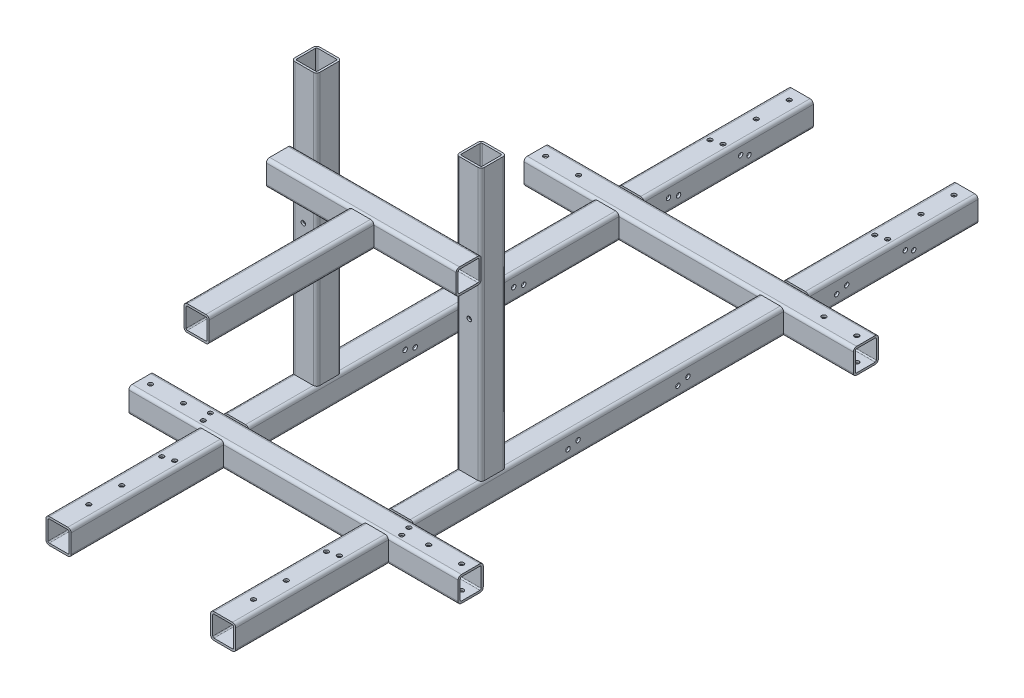
SolidWorks part; units mm, degrees
material "Alumina"
ref_plane "Front Plane" through (0, 0, 0) normal (0, 0, 1) x (1, 0, 0)
ref_plane "Top Plane" through (0, 0, 0) normal (0, 1, 0) x (1, 0, 0)
ref_plane "Right Plane" through (0, 0, 0) normal (1, 0, 0) x (0, 0, -1)
ref_plane "Bottom Face" through (0, 0, 0) normal (0, 1, 0) x (1, 0, 0)
ref_plane "Top Face" through (0, 38.1, 0) normal (0, 1, 0) x (1, 0, 0)
ref_plane "Mid Plane" through (0, 19.05, 0) normal (0, 1, 0) x (1, 0, 0)
ref_plane "Front Face" through (0, 0, 500) normal (0, 0, 1) x (1, 0, 0)
ref_plane "Back Face" through (0, 0, -500) normal (0, 0, 1) x (1, 0, 0)
ref_plane "Left Face" through (250, 0, 0) normal (1, 0, 0) x (0, 0, -1)
ref_plane "Right Face" through (-250, 0, 0) normal (1, 0, 0) x (0, 0, -1)
ref_plane "Divider Plane" through (0, 0, 140) normal (0, 0, 1) x (1, 0, 0)
ref_plane "Max Height Plane" through (0, 450, 0) normal (0, 1, 0) x (1, 0, 0)
ref_plane "Electronics Box Plane" through (0, 338.1, 0) normal (0, 1, 0) x (1, 0, 0)
sketch "Sketch2" plane through (250, 0, 0) normal (1, 0, 0) x (0, 0, -1)
  line L0 (330, 38.1) -> (-330, 38.1) construction
  line L5 (330, 0) -> (-330, 0) construction
  line L6 (0, 220) -> (0, -220) construction
  line L7 (-314.05, 38.1) -> (-285.95, 38.1)
  line L8 (-280.95, 33.1) -> (-280.95, 5)
  line L9 (-315.875, 33.1) -> (-315.875, 5)
  line L10 (-314.05, 3.175) -> (-285.95, 3.175)
  line L11 (-285.95, 0) -> (-314.05, 0)
  line L12 (-319.05, 5) -> (-319.05, 33.1)
  line L13 (-300, 38.1) -> (-300, 0) construction
  line L14 (-319.05, 19.05) -> (-280.95, 19.05) construction
  line L15 (-284.125, 5) -> (-284.125, 33.1)
  line L16 (-285.95, 34.925) -> (-314.05, 34.925)
  line L17 (-300, 34.925) -> (-300, 3.175) construction
  line L18 (-315.875, 19.05) -> (-284.125, 19.05) construction
  arc A0 (-285.95, 38.1) -> (-280.95, 33.1) centre (-285.95, 33.1) cw
  arc A1 (-280.95, 5) -> (-285.95, 0) centre (-285.95, 5) cw
  arc A2 (-314.05, 0) -> (-319.05, 5) centre (-314.05, 5) cw
  arc A3 (-319.05, 33.1) -> (-314.05, 38.1) centre (-314.05, 33.1) cw
  arc A4 (-315.875, 5) -> (-314.05, 3.175) centre (-314.05, 5) ccw
  arc A5 (-285.95, 3.175) -> (-284.125, 5) centre (-285.95, 5) ccw
  arc A6 (-284.125, 33.1) -> (-285.95, 34.925) centre (-285.95, 33.1) ccw
  arc A7 (-314.05, 34.925) -> (-315.875, 33.1) centre (-314.05, 33.1) ccw
  point P20 (-300, 19.05)
  point P39 (-300, 19.05)
  dimension "D1" = 5
  dimension "D2" = 300
  dimension "D3" = 3.175
extrude "Front Cross-Car Member" add sketch "Sketch2" against normal up to surface (500 mm away) up to plane "Right Face"
sketch "Sketch5" plane through (250, 0, 0) normal (1, 0, 0) x (0, 0, -1)
  line L0 (285.95, 38.1) -> (314.05, 38.1)
  line L1 (319.05, 33.1) -> (319.05, 5)
  line L2 (314.05, 0) -> (285.95, 0)
  line L3 (280.95, 5) -> (280.95, 33.1)
  line L4 (300, 38.1) -> (300, 0) construction
  line L5 (280.95, 19.05) -> (319.05, 19.05) construction
  line L6 (285.95, 34.925) -> (314.05, 34.925)
  line L7 (315.875, 33.1) -> (315.875, 5)
  line L8 (314.05, 3.175) -> (285.95, 3.175)
  line L9 (284.125, 5) -> (284.125, 33.1)
  line L10 (300, 34.925) -> (300, 3.175) construction
  line L11 (284.125, 19.05) -> (315.875, 19.05) construction
  line L12 (330, 0) -> (-330, 0) construction
  line L14 (330, 38.1) -> (-330, 38.1) construction
  line L15 (0, 220) -> (0, -220) construction
  arc A0 (314.05, 38.1) -> (319.05, 33.1) centre (314.05, 33.1) cw
  arc A1 (319.05, 5) -> (314.05, 0) centre (314.05, 5) cw
  arc A2 (285.95, 0) -> (280.95, 5) centre (285.95, 5) cw
  arc A3 (280.95, 33.1) -> (285.95, 38.1) centre (285.95, 33.1) cw
  arc A4 (314.05, 34.925) -> (315.875, 33.1) centre (314.05, 33.1) cw
  arc A5 (315.875, 5) -> (314.05, 3.175) centre (314.05, 5) cw
  arc A6 (285.95, 3.175) -> (284.125, 5) centre (285.95, 5) cw
  arc A7 (284.125, 33.1) -> (285.95, 34.925) centre (285.95, 33.1) cw
  point P32 (300, 19.05)
  point P33 (300, 19.05)
  dimension "D2" = 5
  dimension "D1" = 3.175
  dimension "D3" = 300
extrude "Back Cross-Car Member" add sketch "Sketch5" against normal up to surface (500 mm away) separate body up to plane "Right Face"
sketch "Sketch6" plane through (0, 0, -500) normal (0, 0, 1) x (1, 0, 0)
  line L0 (110.95, 38.1) -> (139.05, 38.1)
  line L1 (144.05, 33.1) -> (144.05, 5)
  line L2 (109.125, 33.1) -> (109.125, 5)
  line L3 (110.95, 3.175) -> (139.05, 3.175)
  line L4 (139.05, 0) -> (110.95, 0)
  line L5 (105.95, 5) -> (105.95, 33.1)
  line L6 (125, 38.1) -> (125, 0) construction
  line L7 (105.95, 19.05) -> (144.05, 19.05) construction
  line L8 (140.875, 5) -> (140.875, 33.1)
  line L9 (139.05, 34.925) -> (110.95, 34.925)
  line L10 (125, 34.925) -> (125, 3.175) construction
  line L11 (109.125, 19.05) -> (140.875, 19.05) construction
  line L12 (330, 38.1) -> (-330, 38.1) construction
  line L13 (330, 0) -> (-330, 0) construction
  line L14 (0, -220) -> (0, 220) construction
  arc A0 (139.05, 38.1) -> (144.05, 33.1) centre (139.05, 33.1) cw
  arc A1 (144.05, 5) -> (139.05, 0) centre (139.05, 5) cw
  arc A2 (110.95, 0) -> (105.95, 5) centre (110.95, 5) cw
  arc A3 (105.95, 33.1) -> (110.95, 38.1) centre (110.95, 33.1) cw
  arc A4 (109.125, 5) -> (110.95, 3.175) centre (110.95, 5) ccw
  arc A5 (139.05, 3.175) -> (140.875, 5) centre (139.05, 5) ccw
  arc A6 (140.875, 33.1) -> (139.05, 34.925) centre (139.05, 33.1) ccw
  arc A7 (110.95, 34.925) -> (109.125, 33.1) centre (110.95, 33.1) ccw
  point P16 (125, 19.05)
  point P33 (125, 19.05)
  dimension "D1" = 5
  dimension "D2" = 3.175
  dimension "D3" = 125
extrude "Back Left Along-Car Member" add sketch "Sketch6" along normal blind 180.95 and the other way blind 76.2
extrude "Middle Left Along-Car Member" add sketch "Sketch6<2>" along normal blind 561.9 from offset 219.05
sketch "Sketch6<2>" plane through (0, 0, -500) normal (0, 0, 1) x (1, 0, 0) same geometry as "Sketch6"
extrude "Front Left Along-Car Member" add sketch "Sketch6<3>" along normal blind 231.75 from offset 819.05
sketch "Sketch6<3>" plane through (0, 0, -500) normal (0, 0, 1) x (1, 0, 0) same geometry as "Sketch6"
sketch "Sketch7" plane through (0, 0, -500) normal (0, 0, 1) x (1, 0, 0)
  line L0 (-139.05, 38.1) -> (-110.95, 38.1)
  line L1 (-105.95, 33.1) -> (-105.95, 5)
  line L2 (-140.875, 33.1) -> (-140.875, 5)
  line L3 (-139.05, 3.175) -> (-110.95, 3.175)
  line L4 (-110.95, 0) -> (-139.05, 0)
  line L5 (-144.05, 5) -> (-144.05, 33.1)
  line L6 (-125, 38.1) -> (-125, 0) construction
  line L7 (-144.05, 19.05) -> (-105.95, 19.05) construction
  line L8 (-109.125, 5) -> (-109.125, 33.1)
  line L9 (-110.95, 34.925) -> (-139.05, 34.925)
  line L10 (-125, 34.925) -> (-125, 3.175) construction
  line L11 (-140.875, 19.05) -> (-109.125, 19.05) construction
  line L12 (330, 38.1) -> (-330, 38.1) construction
  line L13 (330, 0) -> (-330, 0) construction
  line L14 (0, -220) -> (0, 220) construction
  arc A0 (-110.95, 38.1) -> (-105.95, 33.1) centre (-110.95, 33.1) cw
  arc A1 (-105.95, 5) -> (-110.95, 0) centre (-110.95, 5) cw
  arc A2 (-139.05, 0) -> (-144.05, 5) centre (-139.05, 5) cw
  arc A3 (-144.05, 33.1) -> (-139.05, 38.1) centre (-139.05, 33.1) cw
  arc A4 (-140.875, 5) -> (-139.05, 3.175) centre (-139.05, 5) ccw
  arc A5 (-110.95, 3.175) -> (-109.125, 5) centre (-110.95, 5) ccw
  arc A6 (-109.125, 33.1) -> (-110.95, 34.925) centre (-110.95, 33.1) ccw
  arc A7 (-139.05, 34.925) -> (-140.875, 33.1) centre (-139.05, 33.1) ccw
  point P16 (-125, 19.05)
  point P33 (-125, 19.05)
  dimension "D1" = 5
  dimension "D2" = 3.175
  dimension "D3" = 125
extrude "Back Right Along-Car Member" add sketch "Sketch7" along normal blind 180.95 and the other way blind 76.2
extrude "Middle Right Along-Car Member" add sketch "Sketch7<2>" along normal blind 561.9 from offset 219.05
sketch "Sketch7<2>" plane through (0, 0, -500) normal (0, 0, 1) x (1, 0, 0) same geometry as "Sketch7"
extrude "Front Right Along-Car Member" add sketch "Sketch7<3>" along normal blind 231.75 from offset 819.05
sketch "Sketch7<3>" plane through (0, 0, -500) normal (0, 0, 1) x (1, 0, 0) same geometry as "Sketch7"
sketch "Sketch8" plane through (0, 38.1, 0) normal (0, 1, 0) x (1, 0, 0)
  line L0 (-139.05, -140) -> (-110.95, -140)
  line L1 (-105.95, -145) -> (-105.95, -173.1)
  line L2 (-140.875, -145) -> (-140.875, -173.1)
  line L3 (-139.05, -174.925) -> (-110.95, -174.925)
  line L4 (-110.95, -178.1) -> (-139.05, -178.1)
  line L5 (-144.05, -173.1) -> (-144.05, -145)
  line L6 (-125, -140) -> (-125, -178.1) construction
  line L7 (-144.05, -159.05) -> (-105.95, -159.05) construction
  line L8 (-109.125, -173.1) -> (-109.125, -145)
  line L9 (-110.95, -143.175) -> (-139.05, -143.175)
  line L10 (-125, -143.175) -> (-125, -174.925) construction
  line L11 (-140.875, -159.05) -> (-109.125, -159.05) construction
  line L12 (-220, -140) -> (220, -140) construction
  line L13 (0, -247.5) -> (0, 247.5) construction
  arc A0 (-110.95, -140) -> (-105.95, -145) centre (-110.95, -145) cw
  arc A1 (-105.95, -173.1) -> (-110.95, -178.1) centre (-110.95, -173.1) cw
  arc A2 (-139.05, -178.1) -> (-144.05, -173.1) centre (-139.05, -173.1) cw
  arc A3 (-144.05, -145) -> (-139.05, -140) centre (-139.05, -145) cw
  arc A4 (-140.875, -173.1) -> (-139.05, -174.925) centre (-139.05, -173.1) ccw
  arc A5 (-110.95, -174.925) -> (-109.125, -173.1) centre (-110.95, -173.1) ccw
  arc A6 (-109.125, -145) -> (-110.95, -143.175) centre (-110.95, -145) ccw
  arc A7 (-139.05, -143.175) -> (-140.875, -145) centre (-139.05, -145) ccw
  point P16 (-125, -159.05)
  point P33 (-125, -159.05)
  dimension "D1" = 5
  dimension "D2" = 3.175
  dimension "D3" = 38.1
  dimension "D4" = 125
extrude "Right Vertical Member" add sketch "Sketch8" along normal up to surface (411.9 mm away) up to plane "Max Height Plane"
sketch "Sketch10" plane through (0, 38.1, 0) normal (0, 1, 0) x (1, 0, 0)
  line L0 (110.95, -140) -> (139.05, -140)
  line L1 (144.05, -145) -> (144.05, -173.1)
  line L2 (109.125, -145) -> (109.125, -173.1)
  line L3 (110.95, -174.925) -> (139.05, -174.925)
  line L4 (139.05, -178.1) -> (110.95, -178.1)
  line L5 (105.95, -173.1) -> (105.95, -145)
  line L6 (125, -140) -> (125, -178.1) construction
  line L7 (105.95, -159.05) -> (144.05, -159.05) construction
  line L8 (140.875, -173.1) -> (140.875, -145)
  line L9 (139.05, -143.175) -> (110.95, -143.175)
  line L10 (125, -143.175) -> (125, -174.925) construction
  line L11 (109.125, -159.05) -> (140.875, -159.05) construction
  line L12 (-220, -140) -> (220, -140) construction
  line L13 (0, -247.5) -> (0, 247.5) construction
  arc A0 (139.05, -140) -> (144.05, -145) centre (139.05, -145) cw
  arc A1 (144.05, -173.1) -> (139.05, -178.1) centre (139.05, -173.1) cw
  arc A2 (110.95, -178.1) -> (105.95, -173.1) centre (110.95, -173.1) cw
  arc A3 (105.95, -145) -> (110.95, -140) centre (110.95, -145) cw
  arc A4 (109.125, -173.1) -> (110.95, -174.925) centre (110.95, -173.1) ccw
  arc A5 (139.05, -174.925) -> (140.875, -173.1) centre (139.05, -173.1) ccw
  arc A6 (140.875, -145) -> (139.05, -143.175) centre (139.05, -145) ccw
  arc A7 (110.95, -143.175) -> (109.125, -145) centre (110.95, -145) ccw
  point P16 (125, -159.05)
  point P33 (125, -159.05)
  dimension "D1" = 5
  dimension "D2" = 3.175
  dimension "D3" = 38.1
  dimension "D4" = 125
extrude "Left Vertical Member" add sketch "Sketch10" along normal up to surface (411.9 mm away) up to plane "Max Height Plane"
sketch "Sketch11" plane through (250, 0, 0) normal (1, 0, 0) x (0, 0, -1)
  line L0 (-211.2, 338.1) -> (-183.1, 338.1)
  line L1 (-178.1, 333.1) -> (-178.1, 305)
  line L2 (-213.025, 333.1) -> (-213.025, 305)
  line L3 (-211.2, 303.175) -> (-183.1, 303.175)
  line L4 (-183.1, 300) -> (-211.2, 300)
  line L5 (-216.2, 305) -> (-216.2, 333.1)
  line L6 (-197.15, 338.1) -> (-197.15, 300) construction
  line L7 (-216.2, 319.05) -> (-178.1, 319.05) construction
  line L8 (-181.275, 305) -> (-181.275, 333.1)
  line L9 (-183.1, 334.925) -> (-211.2, 334.925)
  line L10 (-197.15, 334.925) -> (-197.15, 303.175) construction
  line L11 (-213.025, 319.05) -> (-181.275, 319.05) construction
  line L12 (-140, 220) -> (-140, -220) construction
  line L13 (330, 338.1) -> (-330, 338.1) construction
  arc A0 (-183.1, 338.1) -> (-178.1, 333.1) centre (-183.1, 333.1) cw
  arc A1 (-178.1, 305) -> (-183.1, 300) centre (-183.1, 305) cw
  arc A2 (-211.2, 300) -> (-216.2, 305) centre (-211.2, 305) cw
  arc A3 (-216.2, 333.1) -> (-211.2, 338.1) centre (-211.2, 333.1) cw
  arc A4 (-213.025, 305) -> (-211.2, 303.175) centre (-211.2, 305) ccw
  arc A5 (-183.1, 303.175) -> (-181.275, 305) centre (-183.1, 305) ccw
  arc A6 (-181.275, 333.1) -> (-183.1, 334.925) centre (-183.1, 333.1) ccw
  arc A7 (-211.2, 334.925) -> (-213.025, 333.1) centre (-211.2, 333.1) ccw
  point P16 (-197.15, 319.05)
  point P33 (-197.15, 319.05)
  dimension "D1" = 5
  dimension "D2" = 3.175
  dimension "D3" = 38.1
  dimension "D4" = 38.1
extrude "Upper Cross-Car Member" add sketch "Sketch11" against normal blind 288.1 from offset 105.95 offset against normal yes
sketch "Sketch12" plane through (0, 0, 140) normal (0, 0, 1) x (1, 0, 0)
  line L0 (-14.05, 338.1) -> (14.05, 338.1)
  line L1 (19.05, 333.1) -> (19.05, 305)
  line L2 (-15.875, 333.1) -> (-15.875, 305)
  line L3 (-14.05, 303.175) -> (14.05, 303.175)
  line L4 (14.05, 300) -> (-14.05, 300)
  line L5 (-19.05, 305) -> (-19.05, 333.1)
  line L6 (0, 338.1) -> (0, 300) construction
  line L7 (-19.05, 319.05) -> (19.05, 319.05) construction
  line L8 (15.875, 305) -> (15.875, 333.1)
  line L9 (14.05, 334.925) -> (-14.05, 334.925)
  line L10 (0, 334.925) -> (0, 303.175) construction
  line L11 (-15.875, 319.05) -> (15.875, 319.05) construction
  line L12 (330, 338.1) -> (-330, 338.1) construction
  line L13 (0, -247.5) -> (0, 247.5) construction
  arc A0 (14.05, 338.1) -> (19.05, 333.1) centre (14.05, 333.1) cw
  arc A1 (19.05, 305) -> (14.05, 300) centre (14.05, 305) cw
  arc A2 (-14.05, 300) -> (-19.05, 305) centre (-14.05, 305) cw
  arc A3 (-19.05, 333.1) -> (-14.05, 338.1) centre (-14.05, 333.1) cw
  arc A4 (-15.875, 305) -> (-14.05, 303.175) centre (-14.05, 305) ccw
  arc A5 (14.05, 303.175) -> (15.875, 305) centre (14.05, 305) ccw
  arc A6 (15.875, 333.1) -> (14.05, 334.925) centre (14.05, 333.1) ccw
  arc A7 (-14.05, 334.925) -> (-15.875, 333.1) centre (-14.05, 333.1) ccw
  point P16 (0, 319.05)
  point P33 (0, 319.05)
  dimension "D1" = 5
  dimension "D2" = 3.175
  dimension "D3" = 38.1
extrude "E-Box Platform Base" add sketch "Sketch12" along normal blind 250 from offset 76.2
sketch "Sketch13" plane through (0, 0, 140) normal (0, 0, -1) x (-1, 0, 0)
  circle A2 centre (126.05, 244.1) radius 3.3782
  circle A3 centre (-125.95, 244.1) radius 3.3782
extrude "Cut-Extrude1" cut sketch "Sketch13" against normal up to surface (38.1 mm away) up to face at (125, 171.55, 178.1)
sketch "Sketch14" plane through (0, 38.1, 0) normal (0, 1, 0) x (1, 0, 0)
  circle A0 centre (-132.62, -386.5) radius 3.3782
  circle A1 centre (-117.38, -382.1) radius 3.3782
  circle A2 centre (-152.9, -292.38) radius 3.3782
  circle A3 centre (-148.5, -307.62) radius 3.3782
  circle A8 centre (152.9, -307.62) radius 3.3782
  circle A9 centre (148.5, -292.38) radius 3.3782
  circle A10 centre (117.38, -386.5) radius 3.3782
  circle A11 centre (132.62, -382.1) radius 3.3782
extrude "Cut-Extrude2" cut sketch "Sketch14" against normal up to surface (38.1 mm away) up to face at (125, 0, 434.925)
sketch "Sketch16" plane through (105.95, 0, 0) normal (-1, 0, 0) x (0, 0, 1)
  circle A0 centre (-478.5, 15.24) radius 3.3782
  circle A1 centre (-465.8, 21.59) radius 3.3782
extrude "Cut-Extrude4" cut sketch "Sketch16" along normal up to surface and the other way up to surface up to face at (-144.05, 19.05, -447.625) other way up to face at (144.05, 19.05, -447.625)
sketch "Sketch17" plane through (-144.05, 0, 0) normal (-1, 0, 0) x (0, 0, 1)
  circle A1 centre (43.5864, 20.25) radius 3.3782
  circle A2 centre (28.3464, 15.85) radius 3.3782
  circle A3 centre (-356.2832, 20.25) radius 3.3782
  circle A4 centre (-371.5232, 15.85) radius 3.3782
  circle A5 centre (-121.1547, 20.25) radius 3.3782
  circle A6 centre (-136.3947, 15.85) radius 3.3782
sketch "Sketch18" plane through (0, 38.1, 0) normal (0, 1, 0) x (1, 0, 0)
  circle A0 centre (-132.62, 446) radius 3.3782
  circle A1 centre (-117.38, 450.4) radius 3.3782
  circle A2 centre (117.38, 446) radius 3.3782
  circle A3 centre (132.62, 450.4) radius 3.3782
sketch "Sketch19" plane through (144.05, 0, 0) normal (1, 0, 0) x (0, 0, -1)
  circle A0 centre (-46.3207, 15.85) radius 3.3782
  circle A1 centre (-31.0807, 20.25) radius 3.3782
  circle A2 centre (376.8433, 20.25) radius 3.3782
  circle A3 centre (361.6033, 15.85) radius 3.3782
  circle A4 centre (120.5766, 15.85) radius 3.3782
  circle A5 centre (135.8166, 20.25) radius 3.3782
extrude "Cut-Extrude5" cut sketch "Sketch17" against normal up to surface (38.1 mm away) up to face at (-105.95, 19.05, 0)
extrude "Cut-Extrude6" cut sketch "Sketch18" against normal up to surface (38.1 mm away) up to face at (-125, 0, -447.625)
extrude "Cut-Extrude7" cut sketch "Sketch19" against normal up to surface (38.1 mm away) up to face at (105.95, 19.05, 0)
sketch "Sketch20" plane through (0, 38.1, 0) normal (0, 1, 0) x (1, 0, 0)
  circle A0 centre (236.2063, -300) radius 3.38
  circle A1 centre (186.2063, -300) radius 3.38
  circle A2 centre (125, -504.9062) radius 3.38
  circle A3 centre (125, -454.9062) radius 3.38
  circle A4 centre (-125, -504.9063) radius 3.38
  circle A5 centre (-125, -454.9063) radius 3.38
  circle A6 centre (-186.2062, -300) radius 3.38
  circle A7 centre (-236.2062, -300) radius 3.38
  circle A8 centre (236.2062, 300) radius 3.38
  circle A9 centre (186.2062, 300) radius 3.38
  circle A10 centre (-186.2063, 300) radius 3.38
  circle A11 centre (-236.2063, 300) radius 3.38
  circle A12 centre (125, 508.7062) radius 3.38
  circle A13 centre (125, 558.7062) radius 3.38
  circle A14 centre (-125, 508.7062) radius 3.38
  circle A15 centre (-125, 558.7062) radius 3.38
extrude "Cut-Extrude8" cut sketch "Sketch20" against normal up to surface (38.1 mm away) up to face at (-132.62, 0, -449.3782)
equation "\"D1@Front Face\" = \"frameLength@Master Assembly.SLDASM\" / 2"
equation "\"D1@Back Face\" = \"frameLength@Master Assembly.SLDASM\" / 2"
equation "\"D1@Left Face\"=\"frameWidth@Master Assembly.SLDASM\"/2"
equation "\"D1@Right Face\" = \"frameWidth@Master Assembly.SLDASM\" / 2"
equation "\"D1@Top Face\"=\"frameTubeStockHeight@Master Assembly.SLDASM\""
equation "\"D2@Sketch2\"=\"frameMemberDistLength@Master Assembly.SLDASM\"/2"
equation "\"D3@Sketch2\"=\"frameTubeStockWallThickness@Master Assembly.SLDASM\""
equation "\"D1@Sketch5\"=\"frameTubeStockWallThickness@Master Assembly.SLDASM\""
equation "\"D3@Sketch5\"=\"frameMemberDistLength@Master Assembly.SLDASM\"/2"
equation "\"D3@Sketch6\"=\"frameMemberDistWidth@Master Assembly.SLDASM\"/2"
equation "\"D1@Back Left Along-Car Member\"=( \"frameLength@Master Assembly.Assembly\" - \"frameMemberDistLength@Master Assembly.Assembly\" - \"frameTubeStockHeight@Master Assembly.Assembly\" )  / 2"
equation "\"D19@Middle Left Along-Car Member\" = ( \"frameLength@Master Assembly.SLDASM\" - \"frameMemberDistLength@Master Assembly.SLDASM\" + \"frameTubeStockHeight@Master Assembly.SLDASM\" ) / 2"
equation "\"D1@Middle Left Along-Car Member\"=\"frameMemberDistLength@Master Assembly.SLDASM\" - \"frameTubeStockHeight@Master Assembly.SLDASM\""
equation "\"D19@Front Left Along-Car Member\"=( \"frameLength@Master Assembly.SLDASM\" - \"frameMemberDistLength@Master Assembly.SLDASM\" )  / 2 + \"frameMemberDistLength@Master Assembly.SLDASM\" + \"frameTubeStockHeight@Master Assembly.SLDASM\" / 2"
equation "\"D1@Front Left Along-Car Member\" =  ( \"frameLength@Master Assembly.Assembly\" - \"frameMemberDistLength@Master Assembly.Assembly\" - \"frameTubeStockHeight@Master Assembly.Assembly\" )  / 2 + 2in"
equation "\"D3@Sketch7\"=\"frameMemberDistWidth@Master Assembly.SLDASM\"/2"
equation "\"D1@Back Right Along-Car Member\"=(\"frameLength@Master Assembly.SLDASM\" - \"frameMemberDistLength@Master Assembly.SLDASM\" - \"frameTubeStockHeight@Master Assembly.SLDASM\")  / 2"
equation "\"D19@Middle Right Along-Car Member\" = ( \"frameLength@Master Assembly.SLDASM\" - \"frameMemberDistLength@Master Assembly.SLDASM\" + \"frameTubeStockHeight@Master Assembly.SLDASM\" ) / 2"
equation "\"D1@Middle Right Along-Car Member\"=\"frameMemberDistLength@Master Assembly.SLDASM\" - \"frameTubeStockHeight@Master Assembly.SLDASM\""
equation "\"D19@Front Right Along-Car Member\"=( \"frameLength@Master Assembly.SLDASM\" - \"frameMemberDistLength@Master Assembly.SLDASM\" )  / 2 + \"frameMemberDistLength@Master Assembly.SLDASM\" + \"frameTubeStockHeight@Master Assembly.SLDASM\" / 2"
equation "\"D1@Front Right Along-Car Member\"=( \"frameLength@Master Assembly.Assembly\" - \"frameMemberDistLength@Master Assembly.Assembly\" - \"frameTubeStockHeight@Master Assembly.Assembly\" )  / 2 + 2in"
equation "\"D1@Divider Plane\"= \"frameDividerPlaneOffset@Master Assembly.SLDASM\""
equation "\"D3@Sketch8\"=\"frameTubeStockHeight@Master Assembly.SLDASM\""
equation "\"D4@Sketch8\"=\"frameMemberDistWidth@Master Assembly.SLDASM\"/2"
equation "\"D1@Max Height Plane\" = \"frameHeight@Master Assembly.SLDASM\""
equation "\"D4@Sketch10\"=\"frameMemberDistWidth@Master Assembly.SLDASM\"/2"
equation "\"D1@Electronics Box Plane\" = \"eboxPlaneHeight@Master Assembly.SLDASM\""
equation "\"D4@Sketch11\"=\"frameTubeStockHeight@Master Assembly.SLDASM\""
equation "\"D19@Upper Cross-Car Member\" = ( \"frameWidth@Master Assembly.SLDASM\" - \"frameMemberDistWidth@Master Assembly.SLDASM\" - \"frameTubeStockHeight@Master Assembly.SLDASM\" ) / 2"
equation "\"D1@Upper Cross-Car Member\" = \"frameMemberDistWidth@Master Assembly.SLDASM\" + \"frameTubeStockHeight@Master Assembly.SLDASM\""
equation "\"D19@E-Box Platform Base\"= \"frameTubeStockHeight@Master Assembly.SLDASM\" * 2"
equation "\"D2@Sketch6\"=\"frameTubeStockWallThickness@Master Assembly.SLDASM\""
equation "\"D2@Sketch7\"=\"frameTubeStockWallThickness@Master Assembly.SLDASM\""
equation "\"D2@Sketch8\"=\"frameTubeStockWallThickness@Master Assembly.SLDASM\""
equation "\"D3@Sketch10\"=\"frameTubeStockHeight@Master Assembly.SLDASM\""
equation "\"D2@Sketch10\"=\"frameTubeStockWallThickness@Master Assembly.SLDASM\""
equation "\"D3@Sketch11\"=\"frameTubeStockHeight@Master Assembly.SLDASM\""
equation "\"D2@Sketch11\"=\"frameTubeStockWallThickness@Master Assembly.SLDASM\""
equation "\"D3@Sketch12\"=\"frameTubeStockHeight@Master Assembly.SLDASM\""
equation "\"D2@Sketch12\"=\"frameTubeStockWallThickness@Master Assembly.SLDASM\""
